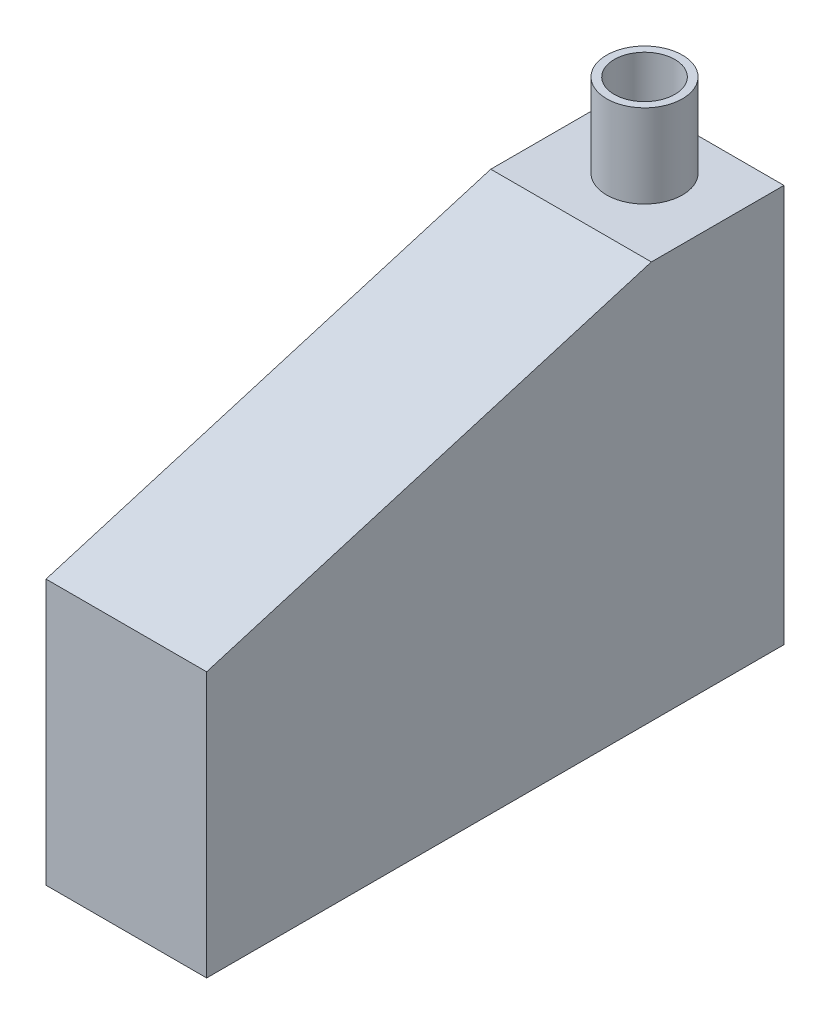
SolidWorks part; units mm, degrees
ref_plane "Płaszczyzna przednia" through (0, 0, 0) normal (0, 0, 1) x (1, 0, 0)
ref_plane "Płaszczyzna górna" through (0, 0, 0) normal (0, 1, 0) x (1, 0, 0)
ref_plane "Płaszczyzna prawa" through (0, 0, 0) normal (1, 0, 0) x (0, 0, -1)
sketch "Szkic1" plane through (0, 0, 0) normal (0, 1, 0) x (1, 0, 0)
  line L1 (20, -75) -> (-20, -75)
  line L2 (20, -75) -> (20, 75)
  line L3 (20, 75) -> (-20, 75)
  line L4 (-20, -75) -> (-20, 75)
  line L5 (20, -75) -> (-20, 75) construction
  line L6 (20, 75) -> (-20, -75) construction
  line L7 (21.2, -76.2) -> (-21.2, -76.2)
  line L8 (21.2, -76.2) -> (21.2, 76.2)
  line L9 (21.2, 76.2) -> (-21.2, 76.2)
  line L10 (-21.2, -76.2) -> (-21.2, 76.2)
  line L11 (21.2, -76.2) -> (-21.2, 76.2) construction
  line L12 (21.2, 76.2) -> (-21.2, -76.2) construction
  point P0 (0, 0)
  point P6 (0, 0)
extrude "Dodanie-wyciągnięcie1" add sketch "Szkic1" along normal blind 70
extrude "Dodanie-wyciągnięcie2" add sketch "Szkic1<2>" along normal blind 2 contours L4 L1 L2 L3 region at (0, 0, 0)
sketch "Szkic1<2>" plane through (0, 0, 0) normal (0, 1, 0) x (1, 0, 0) same geometry as "Szkic1"
sketch "Szkic2" plane through (-21.2, 0, 0) normal (-1, 0, 0) x (0, 0, 1)
  line L0 (-76.2, 70) -> (-76.2, 105)
  line L3 (-76.2, 105) -> (-41.2, 105)
  line L4 (-41.2, 105) -> (76.2, 70)
  line L5 (-75, 103.8) -> (-41.3751, 103.8)
  line L6 (-41.3751, 103.8) -> (71.9998, 70)
  line L8 (-75, 70) -> (-75, 103.8)
  line L13 (-76.2, 70) -> (76.2, 70)
  point P8 (-76.2, 87.5)
  point P11 (-75, 70.537)
  line M9 (76.2, 70) -> (-76.2, 70)
  dimension "D1" = 1.2
  dimension "D2" = 1.2
  dimension "D3" = 1.2
extrude "Dodanie-wyciągnięcie3" add sketch "Szkic2" against normal up to surface (42.4 mm away) contours L0 L3 L4 L13 up to face at (21.2, 35, 0)
extrude "Wytnij-wyciągnięcie1" cut sketch "Szkic2<4>" against normal blind 39.6 from offset 1.2 contours L8 L6 L5 M9 region at (-21.2, 83.3641, -23.9135) offset against normal yes
sketch "Szkic2<4>" plane through (-21.2, 0, 0) normal (-1, 0, 0) x (0, 0, 1) same geometry as "Szkic2"
sketch "Szkic3" plane through (0, 105, 0) normal (0, 1, 0) x (1, 0, 0)
  circle A0 centre (0, 60.5915) radius 10
  circle A1 centre (0, 60.5915) radius 8
extrude "Dodanie-wyciągnięcie4" add sketch "Szkic3" along normal blind 22
extrude "Wytnij-wyciągnięcie2" cut sketch "Szkic3<2>" against normal up to next contours A0 region at (-9.7172, 105, -60.5915)
sketch "Szkic3<2>" plane through (0, 105, 0) normal (0, 1, 0) x (1, 0, 0) same geometry as "Szkic3"
